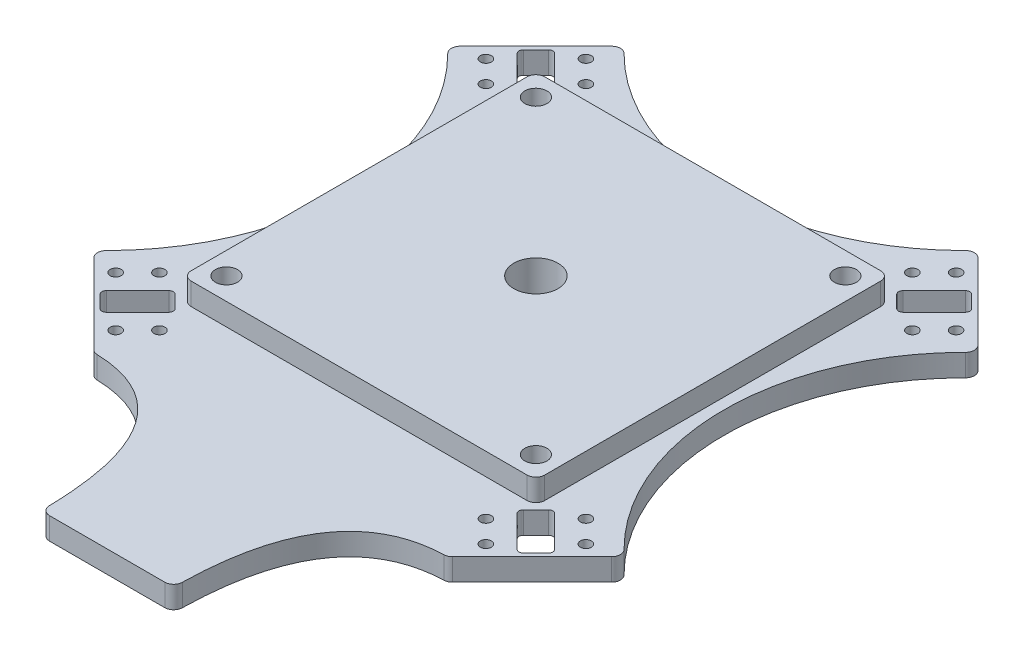
SolidWorks part; units mm, degrees
ref_plane "Front Plane" through (0, 0, 0) normal (0, 0, 1) x (1, 0, 0)
ref_plane "Top Plane" through (0, 0, 0) normal (0, 1, 0) x (1, 0, 0)
ref_plane "Right Plane" through (0, 0, 0) normal (1, 0, 0) x (0, 0, -1)
sketch "Sketch3" plane through (0, 0, 0) normal (0, 1, 0) x (1, 0, 0)
  line L0 (-60, 40) -> (-40, 60)
  line L5 (-60, 60) -> (-50, 50) construction
  line L6 (-60, -60) -> (-50, -50) construction
  line L7 (40, 60) -> (60, 40)
  line L8 (40, -60) -> (60, -40)
  line L9 (-60, -40) -> (-40, -60)
  line L10 (50, 50) -> (60, 60) construction
  line L11 (50, -50) -> (60, -60) construction
  arc A0 (-40, 60) -> (40, 60) centre (0, 96.9643) ccw
  arc A1 (-40, -60) -> (40, -60) centre (0, -96.9643) cw
  arc A2 (-60, -40) -> (-60, 40) centre (-96.9643, 0) ccw
  arc A3 (60, -40) -> (60, 40) centre (96.9643, 0) cw
  point P0 (0, 0)
  point P18 (0, 42.5)
  point P19 (-42.5, 0)
  point P20 (0, -42.5)
  point P21 (42.5, 0)
  dimension "D1" = 120
  dimension "D2" = 120
  dimension "D3" = 17.5
  dimension "D4" = 2.5
  dimension "D5" = 17.5
  dimension "D6" = 17.5
extrude "Boss-Extrude1" add sketch "Sketch3" along normal blind 5
ref_plane "Plane1" through (0, 5, 0) normal (0, 1, 0) x (1, 0, 0)
sketch "Sketch4" plane through (0, 5, 0) normal (0, 1, 0) x (1, 0, 0)
  line L1 (-40, 40) -> (40, 40)
  line L2 (-40, 40) -> (-40, -40)
  line L3 (-40, -40) -> (40, -40)
  line L4 (40, 40) -> (40, -40)
  line L5 (-40, 40) -> (40, -40) construction
  line L6 (-40, -40) -> (40, 40) construction
  point P0 (0, 0)
  dimension "D1" = 80
  dimension "D2" = 80
extrude "Boss-Extrude2" add sketch "Sketch4" along normal blind 5
sketch "Sketch6" plane through (0, 5, 0) normal (0, 1, 0) x (1, 0, 0)
  line L0 (65.5466, 0) -> (-66.5788, 0) construction
  line L1 (0, -65.9767) -> (0, 66.3208) construction
  line L2 (40, 40) -> (-40, 40) construction
  line L3 (-40, 40) -> (-40, -40) construction
  circle A0 centre (-35, 35) radius 2.5
  circle A1 centre (35, 35) radius 2.5
  circle A2 centre (35, -35) radius 2.5
  circle A3 centre (-35, -35) radius 2.5
  dimension "D1" = 5
  dimension "D2" = 5
  dimension "D3" = 5
extrude "Cut-Extrude4" cut sketch "Sketch6" against normal blind 5 and the other way blind 5 contours A0 | A1 | A2 | A3
sketch "Sketch7" plane through (0, 5, 0) normal (0, 1, 0) x (1, 0, 0)
  line L0 (-50, 50) -> (50, -50)
  line L1 (-40, 60) -> (-60, 40) construction
  line L2 (40, -60) -> (60, -40) construction
  line L3 (50, 50) -> (-50, -50)
  line L4 (60, 40) -> (40, 60) construction
  line L5 (-60, -40) -> (-40, -60) construction
  line L6 (47.8787, 50.7071) -> (50.7071, 47.8787)
  line L7 (50.7071, 46.4645) -> (43.636, 39.3934)
  line L8 (42.2218, 39.3934) -> (39.3934, 42.2218)
  line L9 (46.4645, 50.7071) -> (39.3934, 43.636)
  line L10 (39.3934, -42.2218) -> (42.2218, -39.3934)
  line L11 (50.7071, -46.4645) -> (43.636, -39.3934)
  line L12 (50.7071, -47.8787) -> (47.8787, -50.7071)
  line L13 (46.4645, -50.7071) -> (39.3934, -43.636)
  line L14 (-42.2218, -39.3934) -> (-39.3934, -42.2218)
  line L15 (-46.4645, -50.7071) -> (-39.3934, -43.636)
  line L16 (-47.8787, -50.7071) -> (-50.7071, -47.8787)
  line L17 (-50.7071, -46.4645) -> (-43.636, -39.3934)
  line L18 (-39.3934, 42.2218) -> (-42.2218, 39.3934)
  line L19 (-50.7071, 46.4645) -> (-43.636, 39.3934)
  line L20 (-50.7071, 47.8787) -> (-47.8787, 50.7071)
  line L21 (-46.4645, 50.7071) -> (-39.3934, 43.636)
  arc A0 (43.636, 39.3934) -> (42.2218, 39.3934) centre (42.9289, 40.1005) cw
  arc A1 (50.7071, 47.8787) -> (50.7071, 46.4645) centre (50, 47.1716) cw
  arc A2 (39.3934, 43.636) -> (39.3934, 42.2218) centre (40.1005, 42.9289) ccw
  arc A3 (47.8787, 50.7071) -> (46.4645, 50.7071) centre (47.1716, 50) ccw
  arc A4 (43.636, -39.3934) -> (42.2218, -39.3934) centre (42.9289, -40.1005) ccw
  arc A5 (50.7071, -47.8787) -> (50.7071, -46.4645) centre (50, -47.1716) ccw
  arc A6 (47.8787, -50.7071) -> (46.4645, -50.7071) centre (47.1716, -50) cw
  arc A7 (39.3934, -43.636) -> (39.3934, -42.2218) centre (40.1005, -42.9289) cw
  arc A8 (-39.3934, -43.636) -> (-39.3934, -42.2218) centre (-40.1005, -42.9289) ccw
  arc A9 (-47.8787, -50.7071) -> (-46.4645, -50.7071) centre (-47.1716, -50) ccw
  arc A10 (-50.7071, -47.8787) -> (-50.7071, -46.4645) centre (-50, -47.1716) cw
  arc A11 (-43.636, -39.3934) -> (-42.2218, -39.3934) centre (-42.9289, -40.1005) cw
  arc A12 (-43.636, 39.3934) -> (-42.2218, 39.3934) centre (-42.9289, 40.1005) ccw
  arc A13 (-50.7071, 47.8787) -> (-50.7071, 46.4645) centre (-50, 47.1716) ccw
  arc A14 (-47.8787, 50.7071) -> (-46.4645, 50.7071) centre (-47.1716, 50) cw
  arc A15 (-39.3934, 43.636) -> (-39.3934, 42.2218) centre (-40.1005, 42.9289) cw
  circle A16 centre (-41.8683, 53.182) radius 1.25
  circle A17 centre (-36.9185, 48.2322) radius 1.25
  circle A18 centre (-48.2322, 36.9185) radius 1.25
  circle A19 centre (-53.182, 41.8683) radius 1.25
  circle A20 centre (41.8683, 53.182) radius 1.25
  circle A21 centre (36.9185, 48.2322) radius 1.25
  circle A22 centre (48.2322, 36.9185) radius 1.25
  circle A23 centre (53.182, 41.8683) radius 1.25
  circle A24 centre (53.182, -41.8683) radius 1.25
  circle A25 centre (48.2322, -36.9185) radius 1.25
  circle A26 centre (36.9185, -48.2322) radius 1.25
  circle A27 centre (41.8683, -53.182) radius 1.25
  circle A28 centre (-41.8683, -53.182) radius 1.25
  circle A29 centre (-36.9185, -48.2322) radius 1.25
  circle A30 centre (-48.2322, -36.9185) radius 1.25
  circle A31 centre (-53.182, -41.8683) radius 1.25
  point P18 (42.9289, 38.6863)
  point P21 (51.4142, 47.1716)
  point P23 (40.8076, 40.8076)
  point P28 (49.2929, 49.2929)
  point P67 (0, 0)
  point P80 (0, 0)
  point P89 (0, 0)
  point P98 (0, 0)
  point P104 (0, 0)
  dimension "D4" = 1
  dimension "D6" = 2.5
  dimension "D7" = 2.5
  dimension "D1" = 12
  dimension "D2" = 13
  dimension "D3" = 3
  dimension "D8" = 2.5
  dimension "D9" = 5
  dimension "D10" = 2.5
  dimension "D11" = 5
  dimension "D13" = 3
  dimension "D14" = 3
  dimension "D5" = 4
  dimension "D12" = 4
extrude "Cut-Extrude5" cut sketch "Sketch7" against normal blind 5 contours A15 L21 A14 L20 L0 L18 | L20 A13 L19 A12 L18 L0 | A19 | A18 | A16 | A17 | L16 A9 L15 A8 L14 L3 | A11 L17 A10 L16 L3 L14 | A31 | A30 | A28 | A7 L13 A6 L12 L0 L10 | L12 A5 L11 A4 L10 L0 | A24 | L6 A3 L9 A2 L8 L3 | A1 L6 L3 L8 A0 L7 | A20 | A21 | A23 | A22 | A29 | A25 | A27 | A26 region at (-44.0005, 5, -46.1) region at (-46.1, 5, -44.0005) region at (44.0005, 5, -46.1) region at (46.1, 5, -44.0005) region at (46.1, 5, 44.0005) region at (44.0005, 5, 46.1) region at (-44.0005, 5, 46.1) region at (-46.1, 5, 44.0005) region at (-41.8683, 5, -53.182) region at (-36.9185, 5, -48.2322) region at (-48.2322, 5, -36.9185) region at (-53.182, 5, -41.8683) region at (41.8683, 5, -53.182) region at (36.9185, 5, -48.2322) region at (48.2322, 5, -36.9185) region at (53.182, 5, -41.8683) region at (53.182, 5, 41.8683) region at (-41.8683, 5, 53.182) region at (-48.2322, 5, 36.9185) region at (-53.182, 5, 41.8683)
sketch "Sketch8" plane through (0, 0, 0) normal (0, 1, 0) x (1, 0, 0)
  circle A0 centre (0, 0) radius 5
  dimension "D1" = 10
extrude "Cut-Extrude6" cut sketch "Sketch8" along normal blind 10 contours A0
sketch "Sketch9" plane through (0, 5, 0) normal (0, 1, 0) x (1, 0, 0)
  line L2 (-15, -96.9643) -> (15, -96.9643)
  arc A0 (-40, -60) -> (40, -60) centre (0, -96.9643) cw
  spline S0 degree 2 poles (15, -96.9643) (15.041, -60.243) (40, -60) knots 0 0 0 1 1 1
  spline S1 degree 2 poles (-15, -96.9643) (-15.041, -60.243) (-40, -60) knots 0 0 0 1 1 1
  dimension "D1" = 15
  dimension "D2" = 36.9643
extrude "Boss-Extrude3" add sketch "Sketch9" against normal blind 5
fillet "Fillet1" radius 2 10 edges at (-40, 2.5, 60) (-60, 2.5, 40) (-60, 2.5, -40) (-40, 2.5, -60) (40, 2.5, -60) (60, 2.5, -40) (-15, 2.5, 96.9643) (60, 2.5, 40) (40, 2.5, 60) (15, 2.5, 96.9643)
fillet "Fillet2" radius 2 4 edges at (40, 7.5, -40) (40, 7.5, 40) (-40, 7.5, 40) (-40, 7.5, -40)
